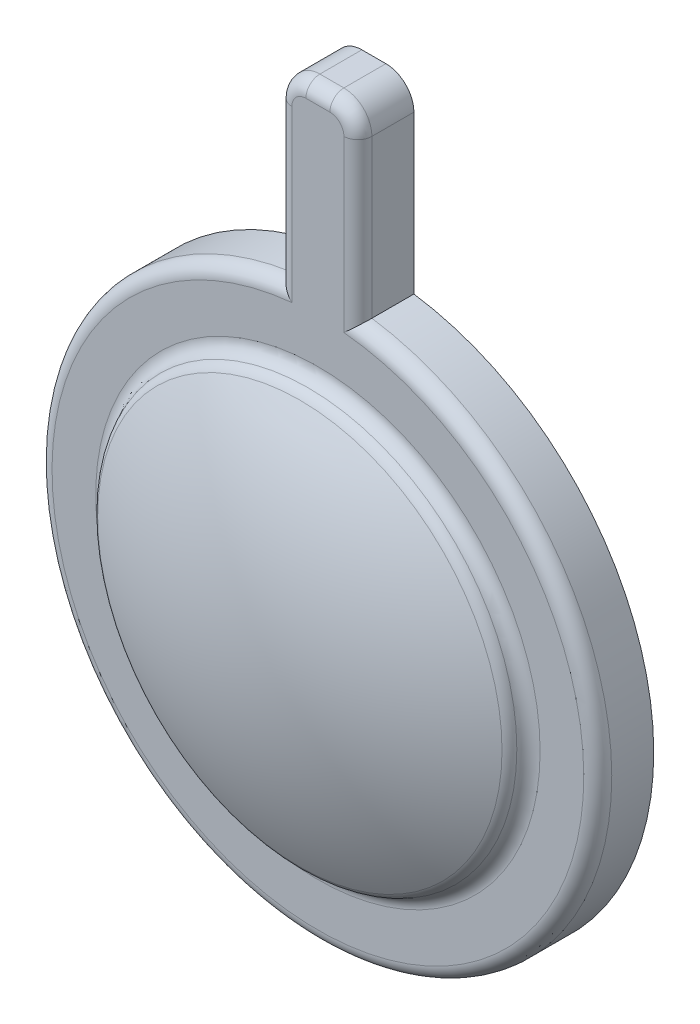
SolidWorks part; units mm, degrees
material "Plastique personnalisé"
ref_plane "Plan de face" through (0, 0, 0) normal (0, 0, 1) x (1, 0, 0)
ref_plane "Plan de dessus" through (0, 0, 0) normal (0, 1, 0) x (1, 0, 0)
ref_plane "Plan de droite" through (0, 0, 0) normal (1, 0, 0) x (0, 0, -1)
sketch "Esquisse1" plane through (0, 0, 0) normal (0, 0, 1) x (1, 0, 0)
  circle A0 centre (0, 0) radius 20
extrude "Boss.-Extru.1" add sketch "Esquisse1" along normal blind 4
sketch "Esquisse4" plane through (0, 0, 0) normal (0, 0, -1) x (-1, 0, 0)
  circle A0 centre (0, 0) radius 4
extrude "Boss.-Extru.3" add sketch "Esquisse4" along normal up to surface (6.843 mm away)
sketch "Esquisse5" plane through (0, 0, 0) normal (0, 0, -1) x (-1, 0, 0)
  line L0 (0, 0) -> (0, 33.0503) construction
  line L2 (2.8583, 14.4082) -> (-2.8583, 14.4082)
  line L3 (2.8583, 14.4082) -> (2.8583, 31.0503)
  line L4 (0.8583, 33.0503) -> (-0.8583, 33.0503)
  line L5 (-2.8583, 14.4082) -> (-2.8583, 31.0503)
  line L6 (2.8583, 14.4082) -> (-2.8583, 33.0503) construction
  line L7 (2.8583, 33.0503) -> (-2.8583, 14.4082) construction
  arc A0 (2.8583, 31.0503) -> (0.8583, 33.0503) centre (0.8583, 31.0503) ccw
  arc A1 (-0.8583, 33.0503) -> (-2.8583, 31.0503) centre (-0.8583, 31.0503) ccw
  point P4 (0, 23.7293)
  dimension "D1" = 2
extrude "Boss.-Extru.4" add sketch "Esquisse5" against normal blind 4
sketch "Esquisse6" plane through (0, 0, 0) normal (0, 0, -1) x (-1, 0, 0)
  circle A0 centre (0, 28.4108) radius 1.5
extrude "Enlèv. mat.-Extru.1" cut sketch "Esquisse6" against normal blind 2.1
sketch "Esquisse7" plane through (0, 0, 0) normal (0, 0, -1) x (-1, 0, 0)
  circle A0 centre (0, -15.504) radius 1.5
extrude "Boss.-Extru.5" add sketch "Esquisse7" along normal blind 1
sketch "Esquisse8" plane through (0, 0, 0) normal (0, 0, -1) x (-1, 0, 0)
  circle A0 centre (0, 0) radius 4.2
extrude "Boss.-Extru.6" add sketch "Esquisse8" along normal up to surface (6.843 mm away) up to face at (4, 0, -6.843)
sketch "Esquisse9" plane through (0, 0, 4) normal (0, 0, 1) x (1, 0, 0)
  circle A0 centre (0, 0) radius 14.9674
extrude "Boss.-Extru.7" add sketch "Esquisse9" along normal blind 1
dome "Dôme1" faces to dome 1 distance 4 reverse direction no elliptical dome no face at (14.9674, 0, 5) parameters "D1"=4
fillet "Congé1" radius 1 1 edges at (14.9674, 0, 5)
fillet "Congé2" radius 1 1 edges at (14.9674, 0, 4)
fillet "Congé3" radius 1 6 edges at (2.8583, 25.4225, 4) (2.2725, 32.4646, 4) (0, 33.0503, 4) (-2.2725, 32.4646, 4) (0, -20, 4) (-2.8583, 25.4225, 4)
